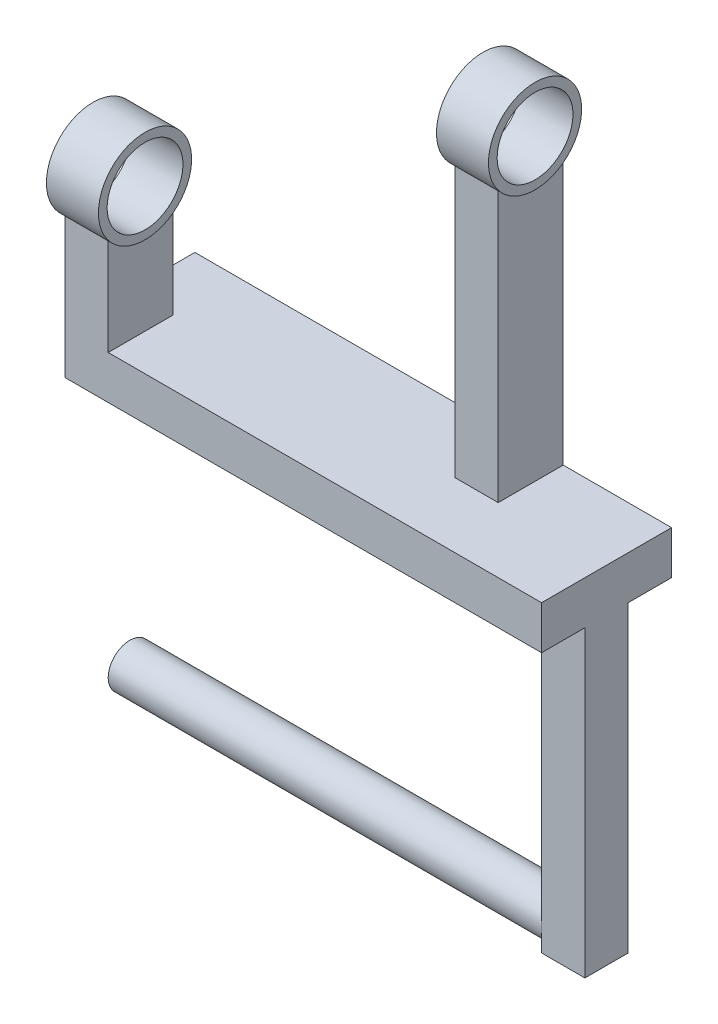
SolidWorks part; units mm, degrees
material "PLA"
ref_plane "Front Plane" through (0, 0, 0) normal (0, 0, 1) x (1, 0, 0)
ref_plane "Top Plane" through (0, 0, 0) normal (0, 1, 0) x (1, 0, 0)
ref_plane "Right Plane" through (0, 0, 0) normal (1, 0, 0) x (0, 0, -1)
sketch "Sketch2" plane through (0, 0, 0) normal (0, 1, 0) x (1, 0, 0)
  line L61 (-60, -15) -> (50, -15)
  line L62 (-60, -15) -> (-60, 15)
  line L63 (-60, 15) -> (50, 15)
  line L64 (50, -15) -> (50, 15)
  dimension "D1" = 30
  dimension "D2" = 110
  dimension "D3" = 60
  dimension "D4" = 15
extrude "Boss-Extrude2" add sketch "Sketch2" along normal blind 10
sketch "Sketch15" plane through (0, 10, 0) normal (0, 1, 0) x (1, 0, 0)
  line L5 (-60, -15) -> (50, -15) construction
  line L6 (-60, -15) -> (-50, -15)
  line L7 (-60, -15) -> (-60, 0)
  line L8 (-60, 0) -> (-50, 0)
  line L9 (-50, -15) -> (-50, 0)
  line L11 (-60, 15) -> (-60, -15) construction
  dimension "D1" = 0
  dimension "D2" = 10
  dimension "D4" = 15
extrude "Boss-Extrude9" add sketch "Sketch15" along normal blind 30
ref_plane "Plane6" through (-55, 0, 0) normal (-1, 0, 0) x (0, 0, 1)
sketch "Sketch17" plane through (-55, 0, 0) normal (-1, 0, 0) x (0, 0, 1)
  line L0 (0, 40) -> (15, 40) construction
  circle A0 centre (7.5, 40) radius 8.75
  dimension "D1" = 17.5
extrude "Extrude-Thin3" add sketch "Sketch17" along normal mid plane 12 thin thin type one direction wall 2
extrude "Cut-Extrude4" cut sketch "Sketch17<2>" against normal mid plane 12
sketch "Sketch17<2>" plane through (-55, 0, 0) normal (-1, 0, 0) x (0, 0, 1) same geometry as "Sketch17"
sketch "Sketch19" plane through (0, 10, 0) normal (0, 1, 0) x (1, 0, 0)
  line L0 (50, 15) -> (-60, 15) construction
  line L1 (15, 15) -> (25, 15)
  line L2 (15, 15) -> (15, 0)
  line L3 (15, 0) -> (25, 0)
  line L4 (25, 15) -> (25, 0)
  line L5 (50, -15) -> (50, 15) construction
  dimension "D1" = 15
  dimension "D2" = 10
  dimension "D3" = 25
extrude "Boss-Extrude11" add sketch "Sketch19" along normal blind 70
ref_plane "Plane7" through (20, 0, 0) normal (-1, 0, 0) x (0, 0, 1)
sketch "Sketch20" plane through (20, 0, 0) normal (-1, 0, 0) x (0, 0, 1)
  line L0 (-15, 80) -> (0, 80) construction
  circle A0 centre (-7.5, 80) radius 8.75
  dimension "D1" = 17.5
extrude "Extrude-Thin4" add sketch "Sketch20" along normal mid plane 12 thin thin type one direction wall 2
extrude "Cut-Extrude5" cut sketch "Sketch20<2>" against normal mid plane 12
sketch "Sketch20<2>" plane through (20, 0, 0) normal (-1, 0, 0) x (0, 0, 1) same geometry as "Sketch20"
sketch "Sketch21" plane through (0, 0, 0) normal (0, -1, 0) x (1, 0, 0)
  line L0 (50, 15) -> (50, -15) construction
  line L1 (50, -5) -> (40, -5)
  line L2 (50, -5) -> (50, 5)
  line L3 (50, 5) -> (40, 5)
  line L4 (40, -5) -> (40, 5)
  line L5 (-60, 15) -> (50, 15) construction
  dimension "D1" = 10
  dimension "D2" = 10
  dimension "D3" = 10
extrude "Boss-Extrude12" add sketch "Sketch21" along normal blind 70
sketch "Sketch22" plane through (40, 0, 0) normal (-1, 0, 0) x (0, 0, 1)
  line L0 (5, -70) -> (5, 0) construction
  line L1 (5, -70) -> (-5, -70) construction
  circle A0 centre (0, -65) radius 5
  dimension "D1" = 10
  dimension "D2" = 5
  dimension "D3" = 5
extrude "Boss-Extrude13" add sketch "Sketch22" along normal blind 100
ref_plane "Plane8" through (0, 70, 0) normal (0, 1, 0) x (1, 0, 0)
sketch "Sketch24" plane through (0, 70, 0) normal (0, 1, 0) x (1, 0, 0)
  line L0 (-49, -7.5) -> (0, -7.5) construction
  line L1 (-49, -18.25) -> (-49, 3.25) construction
ref_plane "MatingPlane" through (0, 11.4078, 29.8742) normal (0, 0.3567, 0.9342) x (1, 0, 0)
